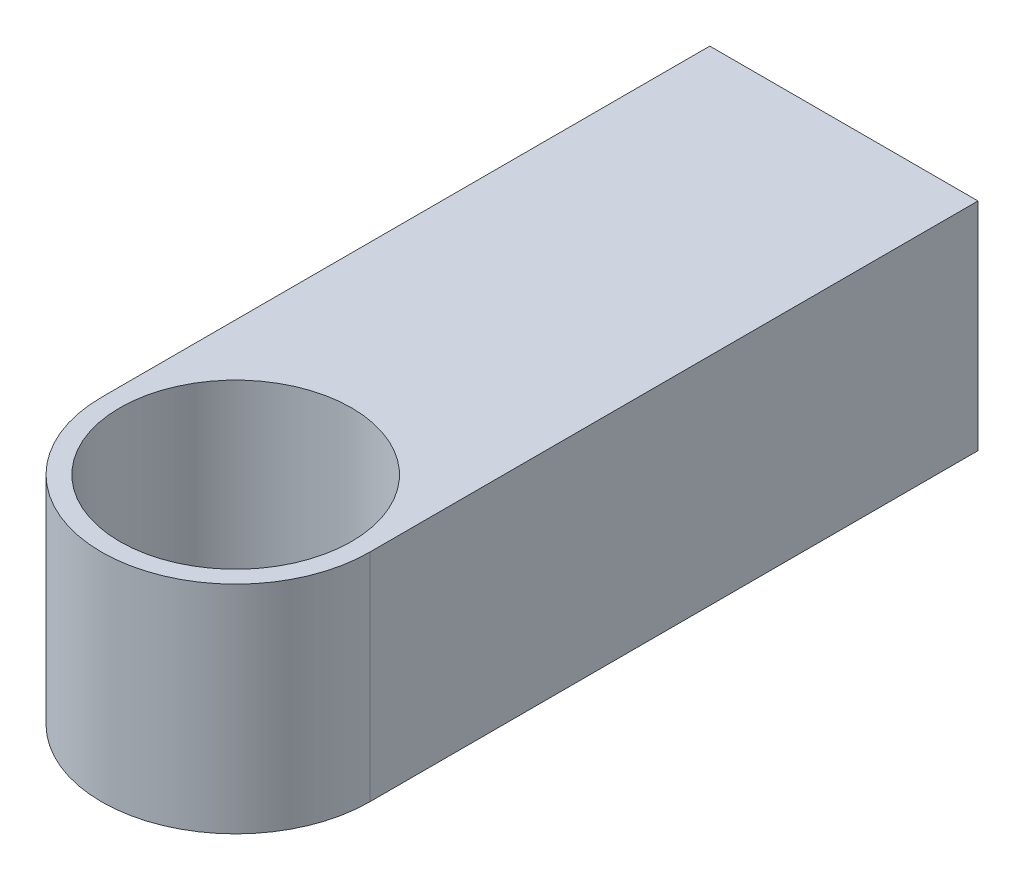
SolidWorks part; units mm, degrees
ref_plane "Front Plane" through (0, 0, 0) normal (0, 0, 1) x (1, 0, 0)
ref_plane "Top Plane" through (0, 0, 0) normal (0, 1, 0) x (1, 0, 0)
ref_plane "Right Plane" through (0, 0, 0) normal (1, 0, 0) x (0, 0, -1)
sketch "Sketch1" plane through (0, 0, 0) normal (0, 0, 1) x (1, 0, 0)
  line L0 (0, 0) -> (22.05, 0)
  line L1 (22.05, 0) -> (22.05, 35.56)
  line L9 (3, 3) -> (19.05, 3)
  line L10 (19.05, 3) -> (19.05, 35.56)
  line L12 (3, 3) -> (0, 3)
  line L13 (0, 3) -> (0, 0) construction
  line L14 (3, 35.56) -> (3, 3) construction
  line L15 (0, 35.56) -> (0, 3) construction
  line L16 (0, 38.56) -> (0, 0) construction
  line L17 (19.05, 35.56) -> (22.05, 35.56)
  line L18 (-19.05, 35.56) -> (-22.05, 35.56) construction
  line L19 (22.05, 38.56) -> (0, 38.56) construction
  line L20 (19.05, 35.56) -> (3, 35.56) construction
  line L21 (22.05, 0) -> (22.05, 38.56) construction
  line L22 (-19.05, 3) -> (-19.05, 35.56) construction
  line L23 (-3, 3) -> (-19.05, 3) construction
  line L24 (-22.05, 0) -> (-22.05, 35.56) construction
  line L25 (0, 0) -> (-22.05, 0) construction
  line L26 (-3, 3) -> (0, 3) construction
  line L27 (0, 3) -> (0, 0)
  dimension "D1" = 38.1
  dimension "D2" = 35.56
  dimension "D3" = 3
revolve "Revolve2" add sketch "Sketch1" angle 360 about L15
sketch "Sketch3" plane through (0, 0, 0) normal (0, -1, 0) x (1, 0, 0)
  circle A0 centre (0, 0) radius 5
  circle A1 centre (0, 0) radius 12.62
  dimension "D1" = 10
  dimension "D2" = 7.62
ref_plane "Plane1" through (0, 17.78, 0) normal (0, -1, 0) x (-1, 0, 0)
sketch "Sketch5" plane through (0, 17.78, 0) normal (0, -1, 0) x (-1, 0, 0)
  line L0 (0, -1000) -> (0, 49000) construction
  line L2 (-22.05, 0) -> (22.05, 0) construction
  line L9 (-22.05, 0) -> (22.05, 0) construction
  line L10 (22.05, 0) -> (22.05, 100)
  line L11 (22.05, 100) -> (-22.05, 100)
  line L12 (-22.05, 100) -> (-22.05, 0)
  arc A1 (22.05, 0) -> (-22.05, 0) centre (0, 0) ccw
  circle A3 centre (0, 0) radius 22.05 construction
  dimension "D1" = 100
extrude "Boss-Extrude3" add sketch "Sketch5" along normal up to surface and the other way up to surface up to face at (-22.05, 0, 0) other way up to face at (-19.05, 35.56, 0)
equation "\"EncoderOuterDiameter\"=1.5"
equation "\"ShaftDiameter\"= 12mm"
equation "\"PendulumDiameter\"=12mm"
equation "\"EncoderShaftDiameter\"= 6mm"
equation "\"EncoderShaftLength\"=15mm+.5in+3mm"
equation "\"ShaftHeightFromTSlot\"= 100mm"
equation "\"D1@Sketch5\"=\"ShaftHeightFromTSlot\""
